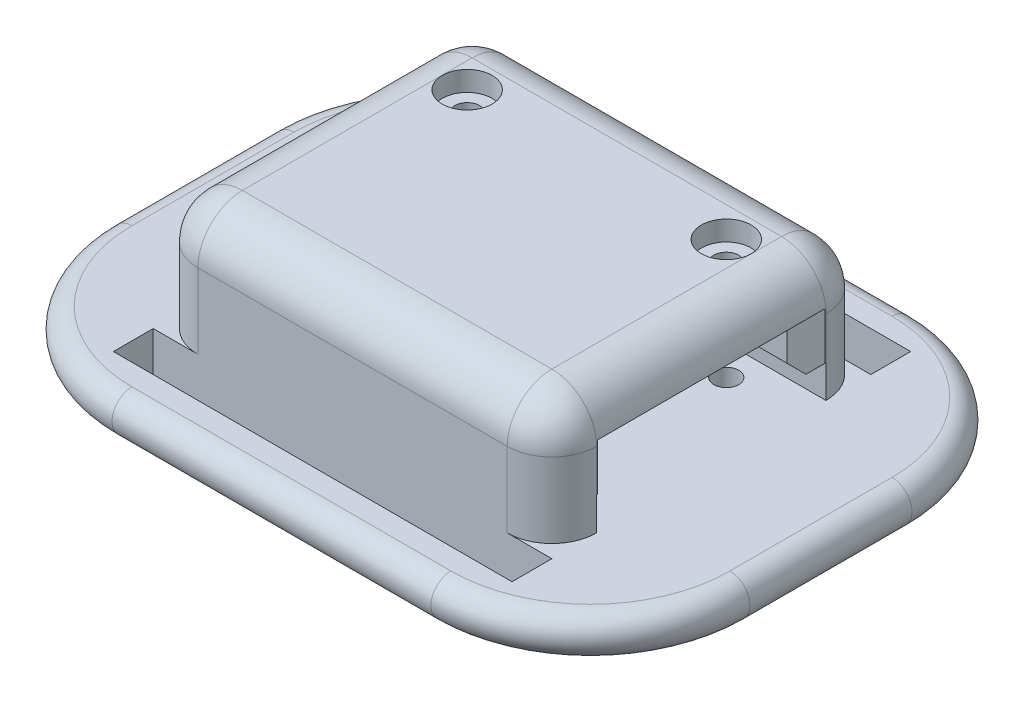
SolidWorks part; units mm, degrees
ref_plane "Front Plane" through (0, 0, 0) normal (0, 0, 1) x (1, 0, 0)
ref_plane "Top Plane" through (0, 0, 0) normal (0, 1, 0) x (1, 0, 0)
ref_plane "Right Plane" through (0, 0, 0) normal (1, 0, 0) x (0, 0, -1)
sketch "Sketch1" plane through (0, 0, 0) normal (0, 1, 0) x (1, 0, 0)
  line L1 (-7.9604, 16.7072) -> (23.7896, 16.7072)
  line L2 (-7.9604, 16.7072) -> (-7.9604, -8.6928)
  line L3 (-7.9604, -8.6928) -> (23.7896, -8.6928)
  line L4 (23.7896, 16.7072) -> (23.7896, -8.6928)
  dimension "D1" = 31.75
  dimension "D2" = 25.4
extrude "Boss-Extrude1" add sketch "Sketch1" along normal blind 12.7
sketch "Sketch2" plane through (23.7896, 0, 0) normal (1, 0, 0) x (0, 0, -1)
  line L0 (-8.6928, 12.7) -> (16.7072, 0) construction
  line L1 (16.7072, 12.7) -> (-8.6928, 0) construction
  line L3 (-5.1209, 3.175) -> (13.1353, 3.175)
  line L4 (-5.1209, 3.175) -> (-5.1209, 9.525)
  line L5 (-5.1209, 9.525) -> (13.1353, 9.525)
  line L6 (13.1353, 3.175) -> (13.1353, 9.525)
  line L7 (-5.1209, 3.175) -> (13.1353, 9.525) construction
  line L8 (-5.1209, 9.525) -> (13.1353, 3.175) construction
  point P4 (4.0072, 6.35)
  point P10 (4.0072, 6.35)
  dimension "D1" = 18.2562
  dimension "D2" = 6.35
extrude "Cut-Extrude3" cut sketch "Sketch2" against normal through all
sketch "Sketch4" plane through (23.7896, 0, 0) normal (1, 0, 0) x (0, 0, -1)
  line L0 (-5.1209, 3.175) -> (13.1353, 3.175) construction
  line L1 (-5.1209, 9.525) -> (-3.5334, 9.525)
  line L2 (-5.1209, 9.525) -> (-5.1209, 4.7625)
  line L3 (-5.1209, 4.7625) -> (-3.5334, 4.7625)
  line L4 (-3.5334, 9.525) -> (-3.5334, 4.7625)
  line L5 (4.0072, 9.525) -> (4.0072, 3.175) construction
  line L6 (13.1353, 4.7625) -> (11.5478, 4.7625)
  line L7 (11.5478, 9.525) -> (11.5478, 4.7625)
  line L8 (13.1353, 9.525) -> (11.5478, 9.525)
  line L9 (13.1353, 9.525) -> (13.1353, 4.7625)
  dimension "D1" = 1.5875
  dimension "D2" = 1.5875
extrude "Boss-Extrude2" add sketch "Sketch4" against normal through all
sketch "Sketch5" plane through (0, 3.175, 0) normal (0, 1, 0) x (1, 0, 0)
  line L0 (-4.7854, 13.1353) -> (-2.4042, 13.1353) construction
  line L1 (-4.7854, -5.1209) -> (20.6146, -5.1209) construction
  line L2 (-4.7854, -5.1209) -> (-4.7854, 13.1353) construction
  line L8 (-4.7854, 13.1353) -> (20.6146, 13.1353) construction
  line L9 (20.6146, -5.1209) -> (20.6146, 13.1353) construction
  line L10 (-4.7854, -5.1209) -> (20.6146, 13.1353) construction
  line L11 (-4.7854, 13.1353) -> (20.6146, -5.1209) construction
  line L12 (-2.4042, 13.1353) -> (-2.4042, 10.7541) construction
  line L13 (7.9146, 4.0072) -> (7.9146, 5.4175) construction
  circle A0 centre (-2.4042, 10.7541) radius 0.9922
  circle A1 centre (18.2333, 10.7541) radius 0.9922
  point P0 (7.9146, 4.0072)
  point P1 (7.9146, 4.0072)
  point P6 (7.9146, 4.0072)
  dimension "D1" = 25.4
  dimension "D2" = 18.2562
extrude "Cut-Extrude5" cut sketch "Sketch5" against normal through all and the other way through all
sketch "Sketch6" plane through (0, 0, 0) normal (0, -1, 0) x (1, 0, 0)
  line L1 (-0.0229, -10.7541) -> (-1.2136, -8.6919)
  line L2 (-1.2136, -8.6919) -> (-3.5948, -8.6919)
  line L3 (-3.5948, -8.6919) -> (-4.7854, -10.7541)
  line L4 (-4.7854, -10.7541) -> (-3.5948, -12.8163)
  line L5 (-3.5948, -12.8163) -> (-1.2136, -12.8163)
  line L6 (-1.2136, -12.8163) -> (-0.0229, -10.7541)
  line L7 (20.6146, -10.7541) -> (19.4239, -8.6919)
  line L8 (19.4239, -8.6919) -> (17.0427, -8.6919)
  line L9 (17.0427, -8.6919) -> (15.8521, -10.7541)
  line L10 (15.8521, -10.7541) -> (17.0427, -12.8163)
  line L11 (17.0427, -12.8163) -> (19.4239, -12.8163)
  line L12 (19.4239, -12.8163) -> (20.6146, -10.7541)
  circle A0 centre (-2.4042, -10.7541) radius 2.3813 construction
  circle A1 centre (18.2333, -10.7541) radius 2.3813 construction
extrude "Cut-Extrude6" cut sketch "Sketch6" against normal blind 1.5875
sketch "Sketch7" plane through (0, 12.7, 0) normal (0, 1, 0) x (1, 0, 0)
  circle A0 centre (-2.4042, 10.7541) radius 1.9844
  circle A1 centre (18.2333, 10.7541) radius 1.9844
extrude "Cut-Extrude7" cut sketch "Sketch7" against normal blind 1.5875
sketch "Sketch8" plane through (0, 0, 0) normal (0, -1, 0) x (1, 0, 0)
  line L1 (-17.4854, -23.1602) -> (33.3146, -23.1602)
  line L2 (-17.4854, -23.1602) -> (-17.4854, 15.1457)
  line L3 (-17.4854, 15.1457) -> (33.3146, 15.1457)
  line L4 (33.3146, -23.1602) -> (33.3146, 15.1457)
  line L5 (-17.4854, -23.1602) -> (33.3146, 15.1457) construction
  line L6 (-17.4854, 15.1457) -> (33.3146, -23.1602) construction
  line L7 (-7.9604, 8.6928) -> (23.7896, 8.6928)
  line L8 (-7.9604, 8.6928) -> (-7.9604, -16.7072)
  line L9 (-7.9604, -16.7072) -> (23.7896, -16.7072)
  line L10 (23.7896, 8.6928) -> (23.7896, -16.7072)
  point P0 (7.9146, -4.0072)
  point P9 (0, 0)
  point P10 (7.9146, -4.0072)
extrude "Boss-Extrude3" add sketch "Sketch8" against normal up to surface (3.175 mm away) contours L8 L7 L10 L9 | L2 L1 L4 L3 up to face at (-2.4042, 3.175, -11.7463)
sketch "Sketch10" plane through (0, 3.175, 0) normal (0, 1, 0) x (1, 0, 0)
  line L0 (-7.9604, 4.0072) -> (23.7896, 4.0072) construction
  line L1 (-7.9604, 16.7072) -> (23.7896, 16.7072)
  line L2 (-7.9604, 16.7072) -> (-7.9604, 19.8822)
  line L3 (-7.9604, 19.8822) -> (23.7896, 19.8822)
  line L4 (23.7896, 16.7072) -> (23.7896, 19.8822)
  line L5 (-7.9604, -11.8678) -> (23.7896, -11.8678)
  line L6 (23.7896, -8.6928) -> (23.7896, -11.8678)
  line L7 (-7.9604, -8.6928) -> (23.7896, -8.6928)
  line L8 (-7.9604, -8.6928) -> (-7.9604, -11.8678)
  dimension "D1" = 3.175
extrude "Cut-Extrude8" cut sketch "Sketch10" against normal through all
fillet "Fillet6" radius 12.7 4 edges at (-17.4854, 1.5875, 15.1457) (-17.4854, 1.5875, -23.1602) (33.3146, 1.5875, -23.1602) (33.3146, 1.5875, 15.1457)
chamfer "Chamfer1" distance 1.016 angle 45 6 edges at (-5.48, 4.7625, -11.5478) (-7.9604, 4.7625, -12.3416) (-7.9604, 4.7625, 4.3272) (7.9146, 4.7625, 3.5334) (23.7896, 4.7625, 4.3272) (23.7896, 4.7625, -12.3416)
chamfer "Chamfer2" distance 1.524 angle 45 4 edges at (-7.9604, 7.6518, -11.5478) (-7.9604, 7.6517, 3.5334) (23.7896, 7.6517, 3.5334) (23.7896, 7.6518, -11.5478)
fillet "Fillet7" radius 3.556 8 edges at (7.9146, 12.7, 8.6928) (23.7896, 7.9375, 8.6928) (23.7896, 12.7, -4.0072) (23.7896, 7.9375, -16.7072) (-7.9604, 12.7, -4.0072) (7.9146, 12.7, -16.7072) (-7.9604, 7.9375, 8.6928) (-7.9604, 7.9375, -16.7072)
fillet "Fillet10" 2 edges at (-13.7657, 0, 11.426) (-13.7657, 3.175, 11.426) type full round first side face at (7.9146, 0, -18.2947) second side face at (7.9146, 3.175, -16.0639) middle face at (-12.4506, 1.5875, 10.1109)
